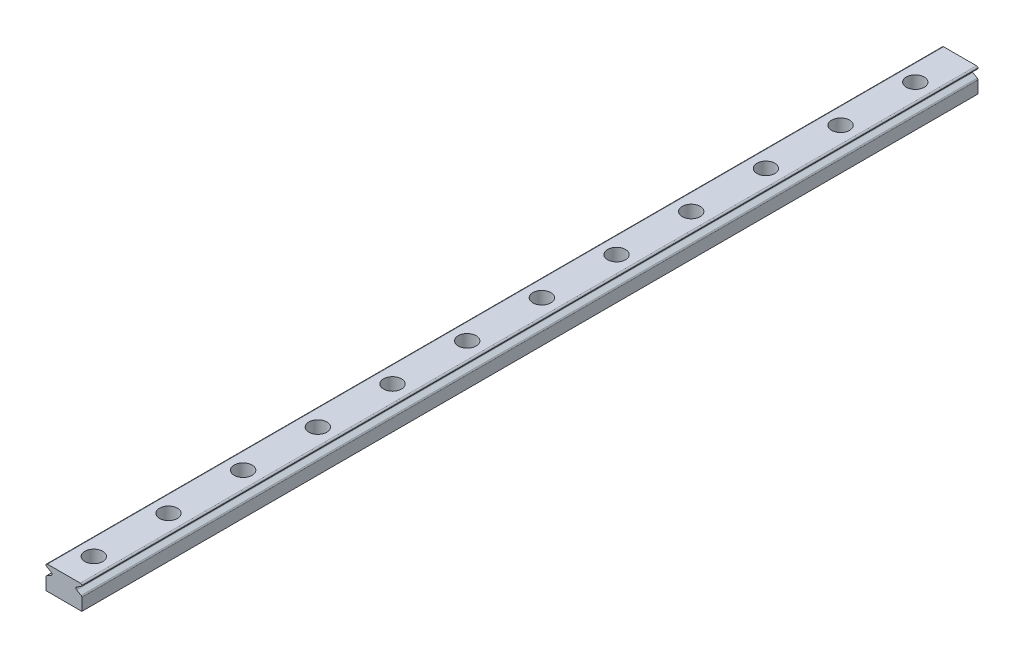
SolidWorks part; units mm, degrees
material "Plain Carbon Steel"
ref_plane "Front Plane" through (0, 0, 0) normal (0, 0, 1) x (1, 0, 0)
ref_plane "Top Plane" through (0, 0, 0) normal (0, 1, 0) x (1, 0, 0)
ref_plane "Right Plane" through (0, 0, 0) normal (1, 0, 0) x (0, 0, -1)
sketch "Sketch1" plane through (0, 0, 0) normal (0, 0, 1) x (1, 0, 0)
  line L4 (0, 0) -> (12, 0)
  line L5 (12, 0) -> (12, 8.4034)
  line L6 (12, 12) -> (0, 12)
  line L7 (0, 12) -> (0, 11.2902)
  line L8 (6, 12) -> (6, 7.6937) construction
  line L9 (6, 7.6937) -> (0, 7.6937) construction
  line L10 (0, 7.6937) -> (12, 7.6937) construction
  line L11 (6, 9.8468) -> (2.5, 9.8468) construction
  line L12 (6, 9.8468) -> (9.5, 9.8468) construction
  line L13 (9.5, 9.8468) -> (12, 11.2902)
  line L22 (9.5, 9.8468) -> (12, 8.4034)
  line L23 (2.5, 9.8468) -> (0, 11.2902)
  line L24 (2.5, 9.8468) -> (0, 8.4034)
  line L27 (12, 11.2902) -> (12, 12)
  line L28 (0, 8.4034) -> (0, 0)
  line L29 (7, 12) -> (7, 0) construction
  dimension "D3" = 3.5
  dimension "D1" = 6
  dimension "D2" = 7.6937
  dimension "D4" = 30
  dimension "D5" = 30
  dimension "D6" = 30
  dimension "D7" = 30
  dimension "D9" = 12
  dimension "D10" = 5
  dimension "D11" = 3.5
extrude "Boss-Extrude2" add sketch "Sketch1" along normal blind 300
fillet "Fillet5" radius 0.5 8 edges at (9.5, 9.8468, 150) (0, 12, 150) (12, 12, 150) (2.5, 9.8468, 150) (12, 8.4034, 150) (0, 8.4034, 150) (12, 11.2902, 150) (0, 11.2902, 150)
sketch "Sketch3" plane through (0, 12, 0) normal (0, 1, 0) x (1, 0, 0)
  line L0 (6, -300) -> (6, -490) construction
  line L1 (11.5, -300) -> (0.5, -300) construction
  line L2 (6, -490) -> (6, -440) construction
  line L3 (6, -440) -> (6, -465) construction
  circle A0 centre (6, -490) radius 3
  circle A1 centre (6, -440) radius 3
  circle A2 centre (6, -415) radius 3
  circle A3 centre (6, -390) radius 3
  circle A4 centre (6, -365) radius 3
  circle A5 centre (6, -340) radius 3
  circle A6 centre (6, -315) radius 3
  circle A7 centre (6, -290) radius 3
  circle A8 centre (6, -265) radius 3
  circle A9 centre (6, -240) radius 3
  circle A10 centre (6, -215) radius 3
  circle A11 centre (6, -190) radius 3
  circle A12 centre (6, -165) radius 3
  circle A13 centre (6, -140) radius 3
  circle A14 centre (6, -115) radius 3
  circle A15 centre (6, -90) radius 3
  circle A16 centre (6, -65) radius 3
  circle A17 centre (6, -40) radius 3
  circle A18 centre (6, -15) radius 3
  circle A19 centre (6, -465) radius 3
  dimension "D1" = 18
extrude "Cut-Extrude2" cut sketch "Sketch3" against normal blind 4.5
sketch "Sketch4" plane through (0, 12, 0) normal (0, 1, 0) x (1, 0, 0)
  line L0 (6, 0) -> (6, -15) construction
  line L1 (11.5, 0) -> (0.5, 0) construction
  circle A0 centre (6, -15) radius 1.75
  circle A1 centre (6, -40) radius 1.75
  circle A2 centre (6, -65) radius 1.75
  circle A3 centre (6, -90) radius 1.75
  circle A4 centre (6, -115) radius 1.75
  circle A5 centre (6, -140) radius 1.75
  circle A6 centre (6, -165) radius 1.75
  circle A7 centre (6, -190) radius 1.75
  circle A8 centre (6, -215) radius 1.75
  circle A9 centre (6, -240) radius 1.75
  circle A10 centre (6, -265) radius 1.75
  circle A11 centre (6, -290) radius 1.75
  circle A12 centre (6, -315) radius 1.75
  circle A13 centre (6, -340) radius 1.75
  circle A14 centre (6, -365) radius 1.75
  circle A15 centre (6, -390) radius 1.75
  circle A16 centre (6, -415) radius 1.75
  circle A17 centre (6, -440) radius 1.75
  circle A18 centre (6, -465) radius 1.75
  circle A19 centre (6, -490) radius 1.75
  dimension "D1" = 20
extrude "Cut-Extrude3" cut sketch "Sketch4" against normal blind 14.5
sketch "Sketch5" plane through (0, 0, 0) normal (0, 0, -1) x (-1, 0, 0)
  line L0 (-12, 0) -> (-12, 4.0574)
  line L2 (-12, 0) -> (-12, 8.1148) construction
  line L3 (-12, 4.0574) -> (0, 4.0574)
  line L4 (0, 8.1148) -> (0, 0) construction
  line L5 (0, 4.0574) -> (0, 0)
  line L6 (0, 0) -> (-12, 0)
extrude "Cut-Extrude4" cut sketch "Sketch5" against normal blind 682.5
